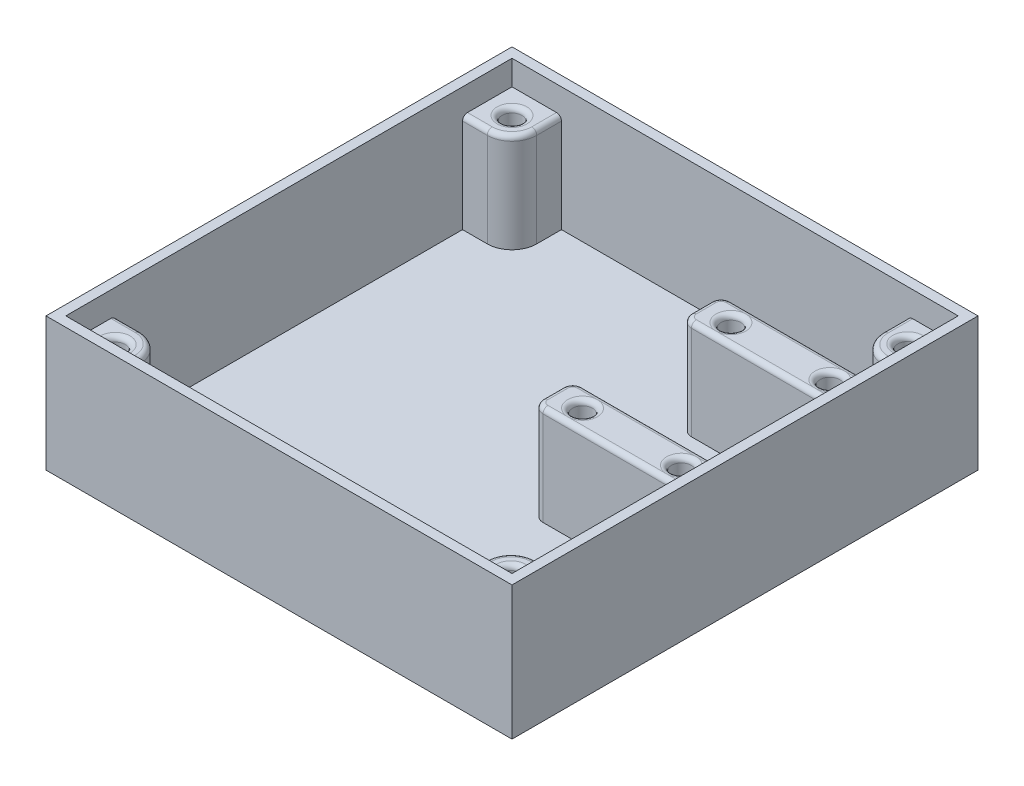
SolidWorks part; units mm, degrees
ref_plane "Front Plane" through (0, 0, 0) normal (0, 0, 1) x (1, 0, 0)
ref_plane "Top Plane" through (0, 0, 0) normal (0, 1, 0) x (1, 0, 0)
ref_plane "Right Plane" through (0, 0, 0) normal (1, 0, 0) x (0, 0, -1)
sketch "Sketch1" plane through (0, 0, 0) normal (0, 1, 0) x (1, 0, 0)
  line L1 (-47.1, -47.1) -> (47.1, -47.1)
  line L2 (-47.1, -47.1) -> (-47.1, 47.1)
  line L3 (-47.1, 47.1) -> (47.1, 47.1)
  line L4 (47.1, -47.1) -> (47.1, 47.1)
  line L5 (-47.1, -47.1) -> (47.1, 47.1) construction
  line L6 (-47.1, 47.1) -> (47.1, -47.1) construction
  point P0 (0, 0)
  dimension "D1" = 94.2
  dimension "D2" = 94.2
extrude "Boss-Extrude1" add sketch "Sketch1" along normal blind 2
sketch "Sketch2" plane through (0, 2, 0) normal (0, 1, 0) x (1, 0, 0)
  line L4 (47.1, -47.1) -> (47.1, 47.1)
  line L5 (47.1, 47.1) -> (-47.1, 47.1)
  line L6 (-47.1, 47.1) -> (-47.1, -47.1)
  line L7 (-47.1, -47.1) -> (47.1, -47.1)
  line L8 (47.1, -47.1) -> (47.1, 47.1)
  line L9 (47.1, 47.1) -> (-47.1, 47.1)
  line L10 (-47.1, 47.1) -> (-47.1, -47.1)
  line L11 (-47.1, -47.1) -> (47.1, -47.1)
  line L16 (45.1, -45.1) -> (45.1, 45.1)
  line L17 (45.1, 45.1) -> (-45.1, 45.1)
  line L18 (-45.1, 45.1) -> (-45.1, -45.1)
  line L19 (-45.1, -45.1) -> (45.1, -45.1)
  line L20 (45.1, -45.1) -> (45.1, 45.1)
  line L21 (45.1, 45.1) -> (-45.1, 45.1)
  line L22 (-45.1, 45.1) -> (-45.1, -45.1)
  line L23 (-45.1, -45.1) -> (45.1, -45.1)
  dimension "D1" = 0
  dimension "D2" = 2
extrude "Boss-Extrude2" add sketch "Sketch2" along normal blind 25
sketch "Sketch3" plane through (0, 2, 0) normal (0, 1, 0) x (1, 0, 0)
  line L1 (-45.1, 45.1) -> (-35.1, 45.1)
  line L2 (-45.1, 45.1) -> (-45.1, 35.1)
  line L3 (-45.1, 35.1) -> (-40.1, 35.1)
  line L4 (-35.1, 45.1) -> (-35.1, 40.1)
  line L29 (45, 45) -> (45, 35)
  line L30 (45, 45) -> (35, 45)
  line L31 (35, 45) -> (35, 40)
  line L32 (45, 35) -> (40, 35)
  line L33 (44.9, -45.1) -> (34.9, -45.1)
  line L34 (44.9, -45.1) -> (44.9, -35.1)
  line L35 (44.9, -35.1) -> (39.9, -35.1)
  line L36 (34.9, -45.1) -> (34.9, -40.1)
  line L37 (-45.2, -45) -> (-45.2, -35)
  line L38 (-45.2, -45) -> (-35.2, -45)
  line L39 (-35.2, -45) -> (-35.2, -40)
  line L40 (-45.2, -35) -> (-40.2, -35)
  arc A0 (-40.1, 35.1) -> (-35.1, 40.1) centre (-40.1, 40.1) ccw
  arc A7 (35, 40) -> (40, 35) centre (40, 40) ccw
  arc A8 (39.9, -35.1) -> (34.9, -40.1) centre (39.9, -40.1) ccw
  arc A9 (-35.2, -40) -> (-40.2, -35) centre (-40.2, -40) ccw
  point P7 (-35.1, 35.1)
  point P29 (3.5, 0)
  point P30 (-1, 0)
  point P31 (0.5, 0)
  point P32 (-0.1, 0)
  dimension "D3" = 5
  dimension "D1" = 10
  dimension "D2" = 10
  dimension "D4" = 4
extrude "Boss-Extrude3" add sketch "Sketch3" along normal blind 20
sketch "Sketch4" plane through (0, 22, 0) normal (0, 1, 0) x (1, 0, 0)
  line L0 (0, 0) -> (16.374, 0) construction
  line L4 (-45.1, 45.1) -> (-45.1, 35.1)
  line L5 (-45.1, 35.1) -> (-40.1, 35.1)
  line L6 (-35.1, 40.1) -> (-35.1, 45.1)
  line L7 (-35.1, 45.1) -> (-45.1, 45.1)
  line L8 (-45.1, 45.1) -> (-45.1, 35.1) construction
  line L9 (-45.1, 35.1) -> (-40.1, 35.1) construction
  line L10 (-35.1, 40.1) -> (-35.1, 45.1) construction
  line L11 (-35.1, 45.1) -> (-45.1, 45.1) construction
  circle A0 centre (-40.1, 40.1) radius 2
  arc A1 (-40.1, 35.1) -> (-35.1, 40.1) centre (-40.1, 40.1) ccw
  arc A2 (-40.1, 35.1) -> (-35.1, 40.1) centre (-40.1, 40.1) ccw construction
  circle A18 centre (39.9, 40.1) radius 2
  circle A21 centre (39.9, -39.9) radius 2 [skipped]
  circle A22 centre (-40.1, -39.9) radius 2 [skipped]
  circle A23 centre (39.9, -40.1) radius 2
  circle A24 centre (-40.1, -40.1) radius 2
  point P16 (-0.1, 0.1)
  point P17 (-0.1, 0)
  point P18 (0, 0)
  point P19 (-0.1, 0.1)
  dimension "D2" = 4
  dimension "D4" = 40
  dimension "D5" = 40
  dimension "D6" = 40
  dimension "D7" = 80.2
  dimension "D1" = 0
  dimension "D3" = 4
extrude "Cut-Extrude1" cut sketch "Sketch4" against normal up to surface (20 mm away) up to face at (39.7929, 2, -39.7929)
sketch "Sketch6" plane through (0, 2, 0) normal (0, 1, 0) x (1, 0, 0)
  line L0 (45.1, -45.1) -> (45.1, 45.1) construction
  line L1 (14.29, 29.97) -> (45.1, 29.97)
  line L3 (14.29, 21.97) -> (45.1, 21.97)
  line L4 (45.1, 29.97) -> (45.1, 21.97)
  line L7 (14.29, -0.03) -> (45.1, -0.03)
  line L9 (14.29, -8.03) -> (45.1, -8.03)
  line L10 (45.1, -0.03) -> (45.1, -8.03)
  line L14 (45.1, 45.1) -> (-35.1, 45.1) construction
  line L15 (12.29, 27.97) -> (12.29, 23.97)
  line L16 (12.29, -2.03) -> (12.29, -6.03)
  circle A0 centre (38.29, 25.97) radius 2
  circle A1 centre (38.29, -4.03) radius 2
  circle A2 centre (18.29, 25.97) radius 2
  circle A3 centre (18.29, -4.03) radius 2
  arc A4 (12.29, -6.03) -> (14.29, -8.03) centre (14.29, -6.03) ccw
  arc A5 (12.29, -2.03) -> (14.29, -0.03) centre (14.29, -2.03) cw
  arc A6 (12.29, 23.97) -> (14.29, 21.97) centre (14.29, 23.97) ccw
  arc A7 (12.29, 27.97) -> (14.29, 29.97) centre (14.29, 27.97) cw
  point P0 (0, 0)
  point P10 (45.1, 25.97)
  point P19 (45.1, -4.03)
  point P26 (0, 0)
  dimension "D2" = 4
  dimension "D3" = 6.81
  dimension "D8" = 2
  dimension "D1" = 8
  dimension "D4" = 19.13
  dimension "D5" = 20
  dimension "D6" = 30
  dimension "D7" = 6
extrude "Boss-Extrude4" add sketch "Sketch6" along normal up to surface (20 mm away) up to face at (39.9, 22, -38.1)
fillet "Fillet1" radius 1 20 edges at (45.1, 12, 0.03) (45.1, 12, 8.03) (45.1, 12, -29.97) (45.1, 12, -21.97) (12.8758, 22, 0.6158) (29.695, 22, 0.03) (45.1, 22, 4.03) (29.695, 22, 8.03) (12.8758, 22, 7.4442) (12.29, 22, 4.03) (18.29, 22, 6.03) (38.29, 22, 6.03) (12.8758, 22, -22.5558) (12.29, 22, -25.97) (12.8758, 22, -29.3842) (29.695, 22, -29.97) (45.1, 22, -25.97) (29.695, 22, -21.97) (38.29, 22, -23.97) (18.29, 22, -23.97)
fillet "Fillet2" radius 1 16 edges at (-35.2, 22, 42.5) (-42.65, 22, 35) (-42.6, 22, -35.1) (-35.1, 22, -42.6) (42.4, 22, 35.1) (34.9, 22, 42.6) (35, 22, -42.5) (42.5, 22, -35) (-40.1, 22, 38.1) (-40.1, 22, -38.1) (39.9, 22, 38.1) (39.9, 22, -38.1) (-36.6645, 22, 36.4645) (-36.5645, 22, -36.5645) (36.3645, 22, 36.5645) (36.4645, 22, -36.4645)
